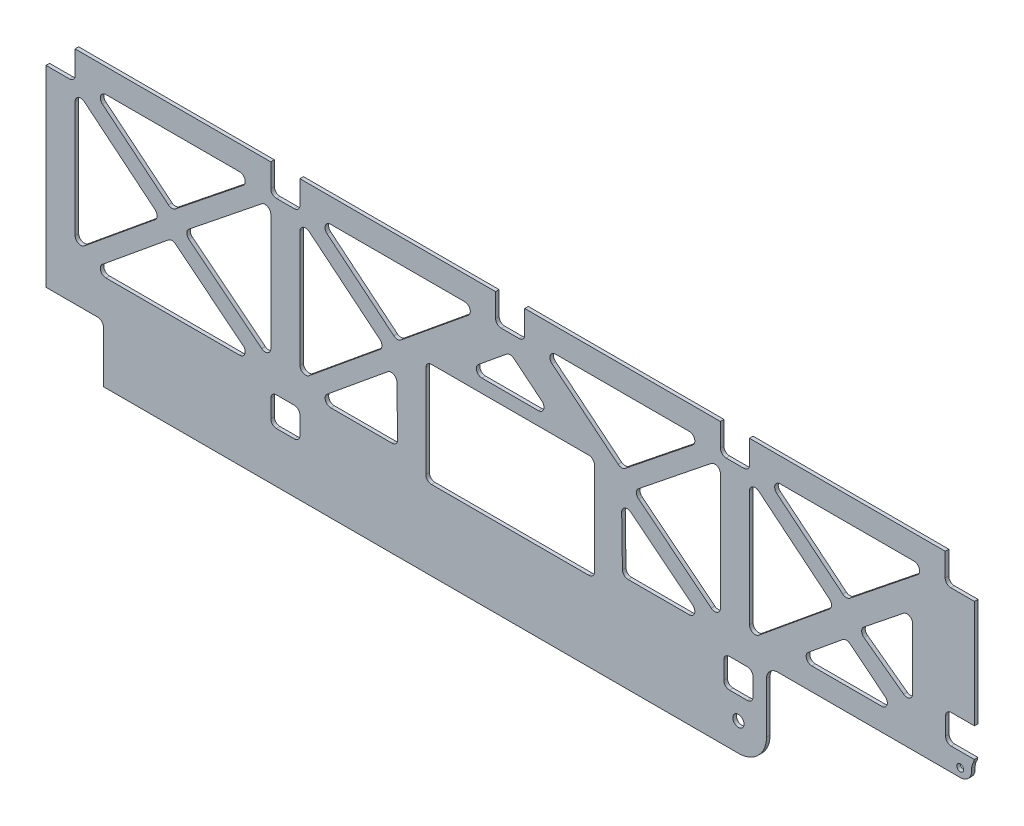
SolidWorks part; units mm, degrees
note: The reader was unsure of these and kept them because the rebuilt part matched: thickness of "Brida base1", "Chapa metálica1", "Chapa metálica23", "Chapa metálica27", "Chapa metálica32", "Chapa metálica33", "Chapa metálica34", "Chapa metálica35", "Chapa metálica36", "Chapa metálica37", "Chapa metálica38", "Chapa metálica39", "Chapa metálica40", "Chapa metálica41", "Chapa metálica42", "Chapa metálica43", "Chapa metálica44", "Chapa metálica45", "Chapa metálica46", "Chapa metálica47", "Chapa metálica48", "Chapa metálica49", "Chapa metálica50", "Chapa metálica51", "Chapa metálica52", "Chapa metálica53", "Chapa metálica54", "Chapa metálica55", "Chapa metálica56", "Chapa metálica57", "Chapa metálica58", "Chapa metálica59", "Chapa metálica60", "Chapa metálica71".
other "Elemento de detalle13"
other "Elemento de detalle19"
other "Carpeta de soldadura"
material "AISI 1010 Barra de acero laminada en caliente"
ref_plane "Alzado" through (0, 0, 0) normal (0, 0, 1) x (1, 0, 0)
ref_plane "Planta" through (0, 0, 0) normal (0, 1, 0) x (1, 0, 0)
ref_plane "Vista lateral" through (0, 0, 0) normal (1, 0, 0) x (0, 0, -1)
sketch "Croquis1" plane through (0, 0, 0) normal (0, 0, 1) x (1, 0, 0)
  line L1 (-634.7218, 129.9029) -> (1017.2782, 129.9029)
  line L2 (-634.7218, 129.9029) -> (-634.7218, -670.0971)
  line L3 (-634.7218, -670.0971) -> (1017.2782, -670.0971)
  line L4 (1017.2782, 129.9029) -> (1017.2782, -670.0971)
  dimension "D1" = 800
  dimension "D2" = 1652
base flange "Brida base1" sketch "Croquis1" thickness 6.35 reverse thickness direction no parameters "D1"=0.7366
ref_plane "Plano1" through (0, 0, 0) normal (0, 1, 0) x (1, 0, 0)
sketch "Croquis14" plane through (0, 0, -6.35) normal (0, 0, 1) x (1, 0, 0)
  line L0 (-634.7218, 129.9029) -> (-634.7218, -670.0971) construction
  line L1 (-634.7218, -670.0971) -> (1017.2782, -670.0971) construction
  line L2 (-634.7218, -174.1971) -> (-582.9218, -174.1971)
  line L3 (965.2782, -174.1971) -> (1028.4048, -174.1971)
  line L4 (-451.2573, -29.958) -> (-582.9218, -29.958) construction
  line L5 (-634.7218, -174.1971) -> (-634.7218, -225.9971)
  line L6 (-634.7218, -225.9971) -> (-582.9218, -225.9971)
  line L7 (-582.9218, -174.1971) -> (-582.9218, -225.9971)
  line L8 (1017.2782, 129.9029) -> (-634.7218, 129.9029) construction
  line L9 (-234.7218, -174.1971) -> (-182.9218, -174.1971)
  line L10 (-234.7218, -174.1971) -> (-234.7218, -225.9971)
  line L11 (1017.2782, 129.9029) -> (-634.7218, 129.9029) construction
  line L12 (-234.7218, -225.9971) -> (-182.9218, -225.9971)
  line L13 (-410.7218, 129.9029) -> (-410.7218, -670.0971) construction
  line L14 (-182.9218, -174.1971) -> (-182.9218, -225.9971)
  line L15 (165.2782, -174.1971) -> (217.0782, -174.1971)
  line L16 (165.2782, -174.1971) -> (165.2782, -225.9971)
  line L17 (165.2782, -225.9971) -> (217.0782, -225.9971)
  line L18 (217.0782, -174.1971) -> (217.0782, -225.9971)
  line L19 (565.2782, -174.1971) -> (617.0782, -174.1971)
  line L20 (565.2782, -174.1971) -> (565.2782, -225.9971)
  line L21 (565.2782, -225.9971) -> (617.0782, -225.9971)
  line L22 (617.0782, -174.1971) -> (617.0782, -225.9971)
  line L23 (165.2782, 130.8029) -> (217.0782, 130.8029)
  line L24 (589.2782, 129.9029) -> (589.2782, -670.0971) construction
  line L25 (89.2782, 129.9029) -> (89.2782, -670.0971) construction
  line L26 (565.2782, 130.8029) -> (617.0782, 130.8029)
  line L27 (565.2782, 130.8029) -> (565.2782, 79.0029)
  line L28 (565.2782, 79.0029) -> (617.0782, 79.0029)
  line L29 (617.0782, 130.8029) -> (617.0782, 79.0029)
  line L30 (-582.9218, 78.1029) -> (-582.9218, -138.0188)
  line L31 (-582.9218, -138.0188) -> (-451.2573, -29.958)
  line L32 (-451.2573, -29.958) -> (-582.9218, 78.1029)
  line L33 (-556.1038, 94.9029) -> (-268.9149, 94.9029)
  line L34 (-268.9149, 94.9029) -> (-410.7218, -24.4164)
  line L35 (-410.7218, -24.4164) -> (-556.1038, 94.9029)
  line L36 (-234.7218, 31.6626) -> (-234.7218, -174.0284)
  line L37 (-234.7218, -174.0284) -> (-327.6777, -27.1786)
  line L38 (965.2782, -174.1971) -> (965.2782, -225.9971)
  line L39 (215.2782, -200.0989) -> (315.2782, -200.0989) construction
  line L40 (617.0782, 78.1029) -> (617.0782, -170.9006)
  line L41 (965.2782, -225.9971) -> (1028.4048, -225.9971)
  line L42 (1028.4048, -174.1971) -> (1028.4048, -225.9971)
  line L43 (-634.7218, 129.9029) -> (-634.7218, -670.0971) construction
  line L44 (768.7748, -46.3989) -> (617.0782, 78.1029)
  line L45 (617.0782, -170.9006) -> (768.7748, -46.3989)
  line L46 (-634.7218, -670.0971) -> (1017.2782, -670.0971) construction
  line L47 (1017.2782, -670.0971) -> (1017.2782, 129.9029) construction
  line L48 (-10.7218, -380.9849) -> (-8.92, -500.3041)
  line L49 (-327.6777, -27.1786) -> (-234.7218, 31.6626)
  line L50 (389.2782, -380.9849) -> (391.08, -500.3041)
  line L51 (191.1782, -255.9971) -> (112.945, -319.9971)
  line L52 (-234.7218, 79.0029) -> (-634.7218, -174.1971) construction
  line L53 (-634.7218, -174.1971) -> (-631.748, -174.0915) construction
  line L54 (112.945, -319.9971) -> (269.4115, -319.9971)
  line L55 (269.4115, -319.9971) -> (191.1782, -255.9971)
  line L56 (191.1782, -225.9971) -> (191.1782, -255.9971) construction
  line L57 (191.1782, -255.9971) -> (191.1782, -319.9971) construction
  line L84 (165.2782, 130.8029) -> (165.2782, 79.0029)
  line L85 (165.2782, 79.0029) -> (217.0782, 79.0029)
  line L86 (217.0782, 130.8029) -> (217.0782, 79.0029)
  line L87 (-234.7218, 130.8029) -> (-182.9218, 130.8029)
  line L88 (-234.7218, 130.8029) -> (-234.7218, 79.0029)
  line L89 (-234.7218, 79.0029) -> (-182.9218, 79.0029)
  line L90 (-182.9218, 130.8029) -> (-182.9218, 79.0029)
  line L91 (-634.7218, 130.8029) -> (-582.9218, 130.8029)
  line L92 (-634.7218, 130.8029) -> (-634.7218, 79.0029)
  line L93 (-634.7218, 79.0029) -> (-582.9218, 79.0029)
  line L94 (-582.9218, 130.8029) -> (-582.9218, 79.0029)
  line L95 (-182.9218, 78.1029) -> (-182.9218, -174.0284)
  line L96 (-182.9218, -174.0284) -> (-31.2252, -46.3989)
  line L97 (-31.2252, -46.3989) -> (-182.9218, 78.1029)
  line L98 (-156.1038, 94.9029) -> (138.2639, 94.9029)
  line L99 (138.2639, 94.9029) -> (-10.7218, -24.4164)
  line L100 (-10.7218, -24.4164) -> (-156.1038, 94.9029)
  line L101 (165.2782, 78.1029) -> (165.2782, -170.9006)
  line L102 (165.2782, -170.9006) -> (9.8215, -46.3989)
  line L103 (9.8215, -46.3989) -> (165.2782, 78.1029)
  line L107 (-31.2252, -46.3989) -> (-182.9218, -46.3989) construction
  line L108 (217.0782, 78.1029) -> (217.0782, -170.9006)
  line L109 (217.0782, -170.9006) -> (368.7748, -46.3989)
  line L110 (368.7748, -46.3989) -> (217.0782, 78.1029)
  line L111 (243.8962, 94.9029) -> (538.2639, 94.9029)
  line L112 (538.2639, 94.9029) -> (389.2782, -24.4164)
  line L113 (389.2782, -24.4164) -> (243.8962, 94.9029)
  line L114 (565.2782, 78.1029) -> (565.2782, -170.9006)
  line L115 (565.2782, -170.9006) -> (409.8215, -46.3989)
  line L116 (409.8215, -46.3989) -> (565.2782, 78.1029)
  line L120 (368.7748, -46.3989) -> (217.0782, -46.3989) construction
  line L124 (643.8962, 94.9029) -> (938.2639, 94.9029)
  line L125 (938.2639, 94.9029) -> (789.2782, -24.4164)
  line L126 (789.2782, -24.4164) -> (643.8962, 94.9029)
  line L127 (965.2782, 78.1029) -> (965.2782, -170.9006)
  line L128 (965.2782, -170.9006) -> (809.8215, -46.3989)
  line L129 (809.8215, -46.3989) -> (965.2782, 78.1029)
  line L134 (-182.9218, -234.5006) -> (-182.9218, -483.5041)
  line L135 (-182.9218, -483.5041) -> (-31.2252, -359.0024)
  line L136 (-31.2252, -359.0024) -> (-182.9218, -234.5006)
  line L137 (-156.1038, -217.7006) -> (138.2639, -217.7006)
  line L138 (138.2639, -217.7006) -> (-9.4746, -338.5606)
  line L139 (-9.4746, -338.5606) -> (-156.1038, -217.7006)
  line L143 (-10.7218, -380.9849) -> (-156.1038, -500.3041)
  line L145 (-156.1038, -500.3041) -> (-8.92, -500.3041)
  line L146 (-31.2252, -359.0024) -> (-182.9218, -359.0024) construction
  line L150 (243.8824, -217.7174) -> (538.2501, -217.7174)
  line L151 (538.2501, -217.7174) -> (389.4543, -336.805)
  line L152 (389.4543, -336.805) -> (243.8824, -217.7174)
  line L153 (565.2782, -234.5006) -> (565.2782, -483.5041)
  line L154 (565.2782, -483.5041) -> (409.8215, -359.0024)
  line L155 (409.8215, -359.0024) -> (565.2782, -234.5006)
  line L157 (538.2639, -500.3041) -> (389.2782, -380.9849)
  line L158 (391.08, -500.3041) -> (538.2639, -500.3041)
  line L160 (617.0782, -234.5006) -> (617.0782, -483.5041)
  line L161 (617.0782, -483.5041) -> (768.7748, -359.0024)
  line L162 (768.7748, -359.0024) -> (617.0782, -234.5006)
  line L163 (643.8962, -217.7006) -> (938.2639, -217.7006)
  line L164 (938.2639, -217.7006) -> (789.2782, -337.0198)
  line L165 (789.2782, -337.0198) -> (643.8962, -217.7006)
  line L166 (907.2782, -294.3999) -> (907.2782, -443.7235)
  line L167 (907.2782, -443.7235) -> (810.208, -372.1413)
  line L168 (810.208, -372.1413) -> (907.2782, -294.3999)
  line L169 (789.2782, -396.7899) -> (699.9586, -470.0971)
  line L170 (880.8119, -470.0971) -> (789.2782, -396.7899)
  line L171 (699.9586, -470.0971) -> (880.8119, -470.0971)
  line L172 (768.7748, -359.0024) -> (617.0782, -359.0024) construction
  line L173 (-582.9218, -234.5006) -> (-582.9218, -483.5041)
  line L174 (-582.9218, -483.5041) -> (-431.2252, -359.0024)
  line L175 (-431.2252, -359.0024) -> (-582.9218, -234.5006)
  line L176 (-556.1038, -217.7006) -> (-261.7361, -217.7006)
  line L177 (-261.7361, -217.7006) -> (-410.7218, -337.0198)
  line L178 (-410.7218, -337.0198) -> (-556.1038, -217.7006)
  line L179 (-234.7218, -234.5006) -> (-234.7218, -483.5041)
  line L180 (-234.7218, -483.5041) -> (-390.1785, -359.0024)
  line L181 (-390.1785, -359.0024) -> (-234.7218, -234.5006)
  line L182 (-410.7218, -380.9849) -> (-556.1038, -500.3041)
  line L183 (-261.7361, -500.3041) -> (-410.7218, -380.9849)
  line L184 (-556.1038, -500.3041) -> (-261.7361, -500.3041)
  line L185 (-431.2252, -359.0024) -> (-582.9218, -359.0024) construction
  dimension "D21" = 30
  dimension "D22" = 64
  dimension "D3" = 0
  dimension "D4" = 2
  dimension "D5" = 51.8
  dimension "D6" = 51.8
  dimension "D7" = 51.8
  dimension "D8" = 304.1
  dimension "D9" = 2
  dimension "D10" = 2
  dimension "D11" = 2
  dimension "D12" = 4
  dimension "D13" = 2
  dimension "D14" = 224
  dimension "D15" = 40
  dimension "D16" = 400
  dimension "D17" = 35
  dimension "D18" = 400
  dimension "D19" = 200
  dimension "D20" = 110
  dimension "D23" = 63
  dimension "D27" = 30
  dimension "D29" = 1000
extrude "Cortar-Extruir1" cut sketch "Croquis14" along normal through all
ref_plane "Plano5" through (0, -200.0971, 0) normal (0, 1, 0) x (1, 0, 0)
ref_plane "Plano6" through (0, -40.0971, 0) normal (0, 1, 0) x (1, 0, 0)
ref_plane "Plano3" through (0, -420.0971, 0) normal (0, -1, 0) x (-1, 0, 0)
fillet "Redondeo1" radius 10 60 edges at (-451.2573, -29.958, -3.175) (-268.9149, 94.9029, -3.175) (-556.1038, 94.9029, -3.175) (880.8119, -470.0971, -3.175) (907.2782, -443.7235, -3.175) (617.0782, -483.5041, -3.175) (699.9586, -470.0971, -3.175) (617.0782, -225.9971, -3.175) (617.0782, -234.5006, -3.175) (643.8962, -217.7006, -3.175) (938.2639, -217.7006, -3.175) (907.2782, -294.3999, -3.175) (768.7748, -359.0024, -3.175) (789.2782, -337.0198, -3.175) (789.2782, -396.7899, -3.175) (810.208, -372.1413, -3.175) (-261.7361, -217.7006, -3.175) (-556.1038, -217.7006, -3.175) (-556.1038, -500.3041, -3.175) (-582.9218, -483.5041, -3.175) (-390.1785, -359.0024, -3.175) (-410.7218, -380.9849, -3.175) (-431.2252, -359.0024, -3.175) (-182.9218, -234.5006, -3.175) (217.0782, -170.9006, -3.175) (243.8962, 94.9029, -3.175) (217.0782, 78.1029, -3.175) (-182.9218, -174.0284, -3.175) (138.2639, -217.7006, -3.175) (-156.1038, -217.7006, -3.175) (-31.2252, -46.3989, -3.175) (-10.7218, -24.4164, -3.175) (165.2782, 78.1029, -3.175) (-156.1038, 94.9029, -3.175) (-261.7361, -500.3041, -3.175) (243.8824, -217.7174, -3.175) (538.2639, -500.3041, -3.175) (409.8215, -359.0024, -3.175) (538.2501, -217.7174, -3.175) (368.7748, -46.3989, -3.175) (409.8215, -46.3989, -3.175) (538.2639, 94.9029, -3.175) (643.8962, 94.9029, -3.175) (789.2782, -24.4164, -3.175) (809.8215, -46.3989, -3.175) (965.2782, -170.9006, -3.175) (938.2639, 94.9029, -3.175) (-182.9218, 78.1029, -3.175) (617.0782, -170.9006, -3.175) (-234.7218, 31.6626, -3.175) (-582.9218, -225.9971, -3.175) (-234.7218, -225.9971, -3.175) (-182.9218, -225.9971, -3.175) (217.0782, -225.9971, -3.175) (165.2782, -225.9971, -3.175) (965.2782, -225.9971, -3.175) (-9.4746, -338.5606, -3.175) (-31.2252, -359.0024, -3.175) (269.4115, -319.9971, -3.175) (191.1782, -255.9971, -3.175)
ref_plane "Plano7" through (0, -476.0971, 0) normal (0, -1, 0) x (-1, 0, 0)
ref_plane "Plano8" through (-410.7218, 0, 0) normal (-1, 0, 0) x (0, 0, 1)
ref_plane "Plano9" through (89.2782, 0, 0) normal (-1, 0, 0) x (0, 0, 1)
ref_plane "Plano10" through (591.1782, 0, 0) normal (-1, 0, 0) x (0, 0, 1)
ref_plane "Plano11" through (0, 104.0029, 0) normal (0, 1, 0) x (1, 0, 0)
sketch "Croquis15" plane through (0, 0, -6.35) normal (0, 0, -1) x (-1, 0, 0)
  line L0 (234.7218, 79.0029) -> (634.7218, -174.1971)
  line L1 (634.7218, -174.1971) -> (723.5953, -174.1971)
  line L2 (723.5953, -174.1971) -> (723.5953, 158.5241)
  line L3 (723.5953, 158.5241) -> (234.7218, 158.5241)
  line L4 (234.7218, 158.5241) -> (234.7218, 79.0029)
extrude "Cortar-Extruir2" cut sketch "Croquis15" against normal blind 10 normal cut yes
sketch "Croquis16" plane through (0, 0, -6.35) normal (0, 0, -1) x (-1, 0, 0)
  line L1 (-1017.2782, -174.1971) -> (834.4945, -174.1971)
  line L2 (-1017.2782, -174.1971) -> (-1017.2782, 472.6355)
  line L3 (-1017.2782, 472.6355) -> (834.4945, 472.6355)
  line L4 (834.4945, -174.1971) -> (834.4945, 472.6355)
extrude "Cortar-Extruir3" cut sketch "Croquis16" against normal blind 10 normal cut yes
sketch "Croquis17" plane through (0, 0, -6.35) normal (0, 0, -1) x (-1, 0, 0)
  line L0 (-965.2782, -215.9971) -> (-611.5841, -506.3181) construction
  line L1 (-1017.2782, -670.0971) -> (-1017.2782, -225.9971) construction
  dimension "D1" = 50.62
hole_wizard "Taladro de margen para M81" [suppressed] positions "Croquis19" profile "Croquis18" hole size "M8" standard "Ansi Metric"
sketch "Croquis19" plane through (0, 0, -6.35) normal (0, 0, -1) x (-1, 0, 0)
  line L0 (-965.2782, -215.9971) -> (-611.5841, -506.3181) construction
  line L1 (-1017.2782, -670.0971) -> (-1017.2782, -225.9971) construction
  line L3 (-591.1782, -225.9971) -> (-591.1782, -587.6273) construction
  line L4 (-575.2782, -225.9971) -> (-607.0782, -225.9971) construction
  line L6 (-175.2782, -225.9971) -> (-207.0782, -225.9971) construction
  line L7 (-191.1782, -225.9971) -> (-191.1782, -615.5767) construction
  line L9 (-965.2782, -215.9971) -> (-611.5841, -506.3181) construction
  line L11 (-217.0782, -215.9971) -> (-570.7724, -506.3181) construction
  line L12 (-165.2782, -215.9971) -> (188.4159, -506.3181) construction
  line L13 (582.9218, -215.9971) -> (229.2276, -506.3181) construction
  point P0 (-944.3982, -233.136)
  point P7 (-878.6971, -287.0651)
  point P9 (-812.9959, -340.9943)
  point P11 (-747.2947, -394.9235)
  point P13 (-681.5935, -448.8526)
  point P15 (-615.8923, -502.7818)
  point P49 (-566.4642, -502.7818)
  point P50 (-500.763, -448.8526)
  point P51 (-435.0618, -394.9235)
  point P52 (-369.3606, -340.9943)
  point P53 (-303.6594, -287.0651)
  point P54 (-237.9582, -233.136)
  point P59 (-144.3982, -233.136)
  point P60 (-78.6971, -287.0651)
  point P61 (-12.9959, -340.9943)
  point P62 (52.7053, -394.9235)
  point P63 (118.4065, -448.8526)
  point P64 (184.1077, -502.7818)
  point P65 (233.5358, -502.7818)
  point P66 (299.237, -448.8526)
  point P67 (364.9382, -394.9235)
  point P68 (430.6394, -340.9943)
  point P69 (496.3406, -287.0651)
  point P70 (562.0418, -233.136)
  dimension "D1" = 72.88
  dimension "D2" = 85
  dimension "D3" = 85
  dimension "D4" = 85
  dimension "D5" = 85
  dimension "D6" = 85
sketch "Croquis18" plane through (944.3982, -233.136, -6.35) normal (1, 0, 0) x (0, 1, 0)
  line L0 (0, 0) -> (0, 6.35)
  line L1 (0, 6.35) -> (4.5, 6.35)
  line L2 (4.5, 6.35) -> (4.5, 0)
  line L5 (4.5, 0) -> (0, 0)
  line L11 (0, -6.35) -> (0, 107.95) construction
  dimension "Diámetro de taladro hasta el siguiente" = 9
  dimension "Profundidad de taladro hasta el siguiente" = 6.35
sketch "Croquis22" plane through (0, 0, 0) normal (0, 0, -1) x (-1, 0, 0)
  line L0 (-1017.2782, -670.0971) -> (-1017.2782, -225.9971) construction
  line L1 (-1017.2782, -670.0971) -> (-647.2782, -670.0971)
  line L2 (-1017.2782, -670.0971) -> (-1017.2782, -510.0971)
  line L3 (-1017.2782, -510.0971) -> (-647.2782, -510.0971)
  line L4 (-647.2782, -670.0971) -> (-647.2782, -510.0971)
  line L5 (-1017.2782, -480.0971) -> (-1012.2782, -480.0971)
  line L6 (-1017.2782, -480.0971) -> (-1017.2782, -510.0971)
  line L7 (-1017.2782, -510.0971) -> (-1012.2782, -510.0971)
  line L8 (-727.9054, -470.0971) -> (-852.3285, -470.0971) construction
  line L9 (-1012.2782, -480.0971) -> (-1012.2782, -510.0971)
  dimension "D1" = 40
  dimension "D2" = 370
  dimension "D3" = 30
  dimension "D4" = 5
extrude "Cortar-Extruir4" cut sketch "Croquis22" along normal blind 10 contours L4 L1 L2 L3 | L5 L9 L3 L6 normal cut yes
fillet "Redondeo2" radius 50 1 edges at (647.2782, -670.0971, -3.175)
fillet "Redondeo4" radius 20 4 edges at (-634.7218, -670.0971, -3.175) (647.2782, -510.0971, -3.175) (1017.2782, -480.0971, -3.175) (1012.2782, -510.0971, -3.175)
sketch "Croquis24" plane through (0, 0, 0) normal (0, 0, 1) x (1, 0, 0)
  line L0 (-614.7218, -670.0971) -> (597.2782, -670.0971) construction
  line L3 (667.2782, -510.0971) -> (992.2782, -510.0971) construction
  line L4 (1012.2782, -480.0971) -> (1012.2782, -490.0971) construction
  line L6 (647.2782, -620.0971) -> (647.2782, -530.0971) construction
  circle A1 centre (597.2782, -620.0971) radius 10
  circle A2 centre (991.8782, -495.0971) radius 6.1
  dimension "D2" = 20
  dimension "D3" = 12.2
  dimension "D6" = 50
  dimension "D1" = 50
  dimension "D4" = 20.4
  dimension "D5" = 15
extrude "Cortar-Extruir5" cut sketch "Croquis24" against normal blind 10 normal cut yes
sketch "Croquis26" plane through (0, 0, 0) normal (0, 0, 1) x (1, 0, 0)
  line L0 (647.2782, -620.0971) -> (647.2782, -530.0971) construction
  line L1 (623.1782, -580.5971) -> (571.3782, -580.5971)
  line L2 (623.1782, -580.5971) -> (623.1782, -528.7971)
  line L3 (623.1782, -528.7971) -> (571.3782, -528.7971)
  line L4 (571.3782, -580.5971) -> (571.3782, -528.7971)
  line L5 (-614.7218, -670.0971) -> (597.2782, -670.0971) construction
  line L6 (1017.7782, -469.6371) -> (965.9782, -469.6371)
  line L7 (1017.7782, -469.6371) -> (1017.7782, -417.8371)
  line L8 (1017.7782, -417.8371) -> (965.9782, -417.8371)
  line L9 (965.9782, -469.6371) -> (965.9782, -417.8371)
  line L10 (-182.9218, -580.5971) -> (-234.7218, -580.5971)
  line L11 (667.2782, -510.0971) -> (992.2782, -510.0971) construction
  line L12 (-182.9218, -580.5971) -> (-182.9218, -528.7971)
  line L13 (991.8782, -417.8371) -> (991.8782, -469.6371) construction
  line L14 (991.8782, -488.9971) -> (991.8782, -501.1971) construction
  line L15 (-182.9218, -528.7971) -> (-234.7218, -528.7971)
  line L16 (-234.7218, -580.5971) -> (-234.7218, -528.7971)
  line L17 (-532.6218, -670.0971) -> (-634.7218, -670.0971)
  line L18 (-532.6218, -670.0971) -> (-532.6218, -567.9971)
  line L19 (-532.6218, -567.9971) -> (-634.7218, -567.9971)
  line L20 (-634.7218, -670.0971) -> (-634.7218, -567.9971)
  line L21 (-208.8218, -528.7971) -> (-208.8218, -225.9971) construction
  line L22 (-224.7218, -225.9971) -> (-192.9218, -225.9971) construction
  line L23 (-634.7218, -225.9971) -> (-634.7218, -650.0971) construction
  circle A0 centre (991.8782, -495.0971) radius 6.1 construction
  dimension "D1" = 24.1
  dimension "D2" = 51.8
  dimension "D3" = 51.8
  dimension "D4" = 89.5
  dimension "D5" = 51.8
  dimension "D6" = 51.8
  dimension "D7" = 40.46
  dimension "D8" = 2
  dimension "D10" = 102.1
  dimension "D9" = 102.1
extrude "Cortar-Extruir6" cut sketch "Croquis26" against normal blind 10 normal cut yes
sketch "Croquis27" plane through (0, 0, 0) normal (0, 0, 1) x (1, 0, 0)
  line L1 (41.1782, -528.7971) -> (341.1782, -528.7971)
  line L2 (41.1782, -528.7971) -> (41.1782, -343.7971)
  line L3 (41.1782, -343.7971) -> (341.1782, -343.7971)
  line L4 (341.1782, -528.7971) -> (341.1782, -343.7971)
  line L5 (41.1782, -528.7971) -> (341.1782, -343.7971) construction
  line L6 (41.1782, -343.7971) -> (341.1782, -528.7971) construction
  line L7 (-182.9218, -528.7971) -> (-234.7218, -528.7971) construction
  line L9 (191.1782, -225.9971) -> (191.1782, -343.7971) construction
  line L11 (175.2782, -225.9971) -> (207.0782, -225.9971) construction
  point P0 (191.1782, -436.2971)
  dimension "D1" = 185
  dimension "D2" = 300
extrude "Cortar-Extruir7" cut sketch "Croquis27" against normal blind 10 contours L3 L4 L1 L2 normal cut yes
fillet "Redondeo5" radius 10 19 edges at (623.1782, -580.5971, -3.175) (571.3782, -580.5971, -3.175) (623.1782, -528.7971, -3.175) (571.3782, -528.7971, -3.175) (965.9782, -469.6371, -3.175) (965.9782, -417.8371, -3.175) (-234.7218, -580.5971, -3.175) (-182.9218, -580.5971, -3.175) (-182.9218, -528.7971, -3.175) (-234.7218, -528.7971, -3.175) (-532.6218, -567.9971, -3.175) (41.1782, -528.7971, -3.175) (341.1782, -528.7971, -3.175) (341.1782, -343.7971, -3.175) (41.1782, -343.7971, -3.175) (391.08, -500.3041, -3.175) (389.2782, -380.9849, -3.175) (-8.92, -500.3041, -3.175) (-10.7218, -380.9849, -3.175)
fillet "Redondeo6" radius 20 1 edges at (1012.2782, -480.0971, -3.175)
sketch "Croquis28" plane through (0, 0, 0) normal (0, 0, 1) x (1, 0, 0)
  line L0 (-582.9218, -174.1971) -> (-234.7218, -174.1971) construction
  line L1 (-617.6412, -95.7669) -> (1013.0871, -95.7669)
  line L2 (-617.6412, -95.7669) -> (-617.6412, -174.6971)
  line L3 (-617.6412, -174.6971) -> (1013.0871, -174.6971)
  line L4 (1013.0871, -95.7669) -> (1013.0871, -174.6971)
  dimension "D1" = 0.5
extrude "Cortar-Extruir8" cut sketch "Croquis28" against normal blind 10
sketch "Líneas de pliegue1" [suppressed] plane through (0, 0, 0) normal (0, 1, 0) x (1, 0, 0)
sketch "Cuadro delimitador1" [suppressed] plane through (0, 0, 0) normal (0, 1, 0) x (1, 0, 0)
sheet metal parameters "Chapa metálica1" thickness 6.35 parameters "D1"=0.7366
flat pattern "Chapa desplegada1" [suppressed]
sketch "Líneas de pliegue2" plane through (0, 0, 0) normal (0, 1, 0) x (1, 0, 0)
sketch3d "Cuadro delimitador2" [suppressed]
  line L0 (-634.7218, -670.0971, 0) -> (1037.2782, -670.0971, 0) construction
  line L1 (-634.7218, 129.9029, 0) -> (1037.2782, 129.9029, 0) construction
  line L2 (-634.7218, -670.0971, 0) -> (-634.7218, 129.9029, 0) construction
  line L3 (1037.2782, -670.0971, 0) -> (1037.2782, 129.9029, 0) construction
sheet metal parameters "Chapa metálica23" thickness 6.35 parameters "D1"=0.7366, "D7"=12.7
flat pattern "Chapa desplegada1"
sketch "Líneas de pliegue2" plane through (0, 0, 0) normal (0, 1, 0) x (1, 0, 0)
sketch3d "Cuadro delimitador2" [suppressed]
  line L0 (-634.7218, -370.0971, 0) -> (1165.2782, -370.0971, 0) construction
  line L1 (-634.7218, 129.9029, 0) -> (1165.2782, 129.9029, 0) construction
  line L2 (-634.7218, -370.0971, 0) -> (-634.7218, 129.9029, 0) construction
  line L3 (1165.2782, -370.0971, 0) -> (1165.2782, 129.9029, 0) construction
sheet metal parameters "Chapa metálica27" thickness 6.35 parameters "D1"=0.7366, "D7"=12.7
flat pattern "Chapa desplegada1"
sketch "Líneas de pliegue2" plane through (0, 0, 0) normal (0, 1, 0) x (1, 0, 0)
sketch3d "Cuadro delimitador2" [suppressed]
  line L0 (-634.7218, -670.0971, 0) -> (1165.2782, -670.0971, 0) construction
  line L1 (-634.7218, 129.9029, 0) -> (1165.2782, 129.9029, 0) construction
  line L2 (-634.7218, -670.0971, 0) -> (-634.7218, 129.9029, 0) construction
  line L3 (1165.2782, -670.0971, 0) -> (1165.2782, 129.9029, 0) construction
sheet metal parameters "Chapa metálica29" thickness 12.7 parameters "D1"=0.7366
flat pattern "Chapa desplegada29"
sketch "Líneas de pliegue4" plane through (0, 0, 0) normal (0, 1, 0) x (1, 0, 0)
sketch3d "Cuadro delimitador4" [suppressed]
  line L0 (-119.0982, -238.1302, 0) -> (165.2782, -238.1302, 0) construction
  line L1 (-119.0982, -2.2285, 0) -> (165.2782, -2.2285, 0) construction
  line L2 (-119.0982, -238.1302, 0) -> (-119.0982, -2.2285, 0) construction
  line L3 (165.2782, -238.1302, 0) -> (165.2782, -2.2285, 0) construction
sheet metal parameters "Chapa metálica30" thickness 12.7 parameters "D1"=0.7366
flat pattern "Chapa desplegada30"
sketch "Líneas de pliegue5" plane through (0, 0, 0) normal (0, 1, 0) x (1, 0, 0)
sketch3d "Cuadro delimitador5" [suppressed]
  line L0 (-485.077, -310.0971, 0) -> (205.2782, -310.0971, 0) construction
  line L1 (-485.077, -211.7375, 0) -> (205.2782, -211.7375, 0) construction
  line L2 (-485.077, -310.0971, 0) -> (-485.077, -211.7375, 0) construction
  line L3 (205.2782, -310.0971, 0) -> (205.2782, -211.7375, 0) construction
sheet metal parameters "Chapa metálica31" thickness 12.7 parameters "D1"=0.7366
flat pattern "Chapa desplegada31"
sketch "Líneas de pliegue6" plane through (0, 0, 0) normal (0, 1, 0) x (1, 0, 0)
sketch3d "Cuadro delimitador6" [suppressed]
  line L0 (-484.7218, -29.6275, 0) -> (205.2782, -29.6275, 0) construction
  line L1 (-484.7218, 69.9029, 0) -> (205.2782, 69.9029, 0) construction
  line L2 (-484.7218, -29.6275, 0) -> (-484.7218, 69.9029, 0) construction
  line L3 (205.2782, -29.6275, 0) -> (205.2782, 69.9029, 0) construction
sheet metal parameters "Chapa metálica32" thickness 6.35 parameters "D1"=0.7366
flat pattern "Chapa desplegada1"
sketch "Líneas de pliegue7" plane through (0, 0, 0) normal (0, 1, 0) x (1, 0, 0)
sketch3d "Cuadro delimitador7" [suppressed]
  line L0 (-634.7218, -670.0971, 0) -> (1165.2782, -670.0971, 0) construction
  line L1 (-634.7218, 129.9029, 0) -> (1165.2782, 129.9029, 0) construction
  line L2 (-634.7218, -670.0971, 0) -> (-634.7218, 129.9029, 0) construction
  line L3 (1165.2782, -670.0971, 0) -> (1165.2782, 129.9029, 0) construction
sheet metal parameters "Chapa metálica33" thickness 6.35 parameters "D1"=0.7366
flat pattern "Chapa desplegada33"
sketch "Líneas de pliegue8" plane through (0, 0, 0) normal (0, 1, 0) x (1, 0, 0)
sketch "Cuadro delimitador8" [suppressed] plane through (0, 0, 0) normal (0, 1, 0) x (1, 0, 0)
sheet metal parameters "Chapa metálica34" thickness 6.35 parameters "D1"=0.7366
flat pattern "Chapa desplegada34"
sketch "Líneas de pliegue9" plane through (0, 0, 0) normal (0, 1, 0) x (1, 0, 0)
sketch "Cuadro delimitador9" [suppressed] plane through (0, 0, 0) normal (0, 1, 0) x (1, 0, 0)
sheet metal parameters "Chapa metálica35" thickness 6.35 parameters "D1"=0.7366
flat pattern "Chapa desplegada1"
sketch "Líneas de pliegue10" plane through (0, 0, 0) normal (0, 1, 0) x (1, 0, 0)
sketch3d "Cuadro delimitador10" [suppressed]
  line L0 (-634.7218, -670.0971, 0) -> (1017.2782, -670.0971, 0) construction
  line L1 (-634.7218, 129.9029, 0) -> (1017.2782, 129.9029, 0) construction
  line L2 (-634.7218, -670.0971, 0) -> (-634.7218, 129.9029, 0) construction
  line L3 (1017.2782, -670.0971, 0) -> (1017.2782, 129.9029, 0) construction
sheet metal parameters "Chapa metálica36" thickness 6.35 parameters "D1"=0.7366
flat pattern "Chapa desplegada36"
sketch "Líneas de pliegue11" plane through (0, 0, 0) normal (0, 1, 0) x (1, 0, 0)
sketch "Cuadro delimitador11" [suppressed] plane through (0, 0, 0) normal (0, 1, 0) x (1, 0, 0)
sheet metal parameters "Chapa metálica37" thickness 6.35 parameters "D1"=0.7366
flat pattern "Chapa desplegada1"
sketch "Líneas de pliegue12" plane through (0, 0, 0) normal (0, 1, 0) x (1, 0, 0)
sketch "Cuadro delimitador12" [suppressed] plane through (0, 0, 0) normal (0, 1, 0) x (1, 0, 0)
sheet metal parameters "Chapa metálica38" thickness 6.35 parameters "D1"=0.7366
flat pattern "Chapa desplegada38"
sketch "Líneas de pliegue13" plane through (0, 0, 0) normal (0, 1, 0) x (1, 0, 0)
sketch "Cuadro delimitador13" [suppressed] plane through (0, 0, 0) normal (0, 1, 0) x (1, 0, 0)
sheet metal parameters "Chapa metálica39" thickness 6.35 parameters "D1"=0.7366
flat pattern "Chapa desplegada39"
sketch "Líneas de pliegue14" plane through (0, 0, 0) normal (0, 1, 0) x (1, 0, 0)
sketch "Cuadro delimitador14" [suppressed] plane through (0, 0, 0) normal (0, 1, 0) x (1, 0, 0)
sheet metal parameters "Chapa metálica40" thickness 6.35 parameters "D1"=0.7366
flat pattern "Chapa desplegada40"
sketch "Líneas de pliegue15" plane through (0, 0, 0) normal (0, 1, 0) x (1, 0, 0)
sketch "Cuadro delimitador15" [suppressed] plane through (0, 0, 0) normal (0, 1, 0) x (1, 0, 0)
sheet metal parameters "Chapa metálica41" thickness 6.35 parameters "D1"=0.7366
flat pattern "Chapa desplegada41"
sketch "Líneas de pliegue16" plane through (0, 0, 0) normal (0, 1, 0) x (1, 0, 0)
sketch "Cuadro delimitador16" [suppressed] plane through (0, 0, 0) normal (0, 1, 0) x (1, 0, 0)
sheet metal parameters "Chapa metálica42" thickness 6.35 parameters "D1"=0.7366
flat pattern "Chapa desplegada42"
sketch "Líneas de pliegue17" plane through (0, 0, 0) normal (0, 1, 0) x (1, 0, 0)
sketch "Cuadro delimitador17" [suppressed] plane through (0, 0, 0) normal (0, 1, 0) x (1, 0, 0)
sheet metal parameters "Chapa metálica43" thickness 6.35 parameters "D1"=0.7366
flat pattern "Chapa desplegada43"
sketch "Líneas de pliegue18" plane through (0, 0, 0) normal (0, 1, 0) x (1, 0, 0)
sketch "Cuadro delimitador18" [suppressed] plane through (0, 0, 0) normal (0, 1, 0) x (1, 0, 0)
sheet metal parameters "Chapa metálica44" thickness 6.35 parameters "D1"=0.7366
flat pattern "Chapa desplegada44"
sketch "Líneas de pliegue19" plane through (0, 0, 0) normal (0, 1, 0) x (1, 0, 0)
sketch "Cuadro delimitador19" [suppressed] plane through (0, 0, 0) normal (0, 1, 0) x (1, 0, 0)
sheet metal parameters "Chapa metálica45" thickness 6.35 parameters "D1"=0.7366
flat pattern "Chapa desplegada45"
sketch "Líneas de pliegue20" plane through (0, 0, 0) normal (0, 1, 0) x (1, 0, 0)
sketch "Cuadro delimitador20" [suppressed] plane through (0, 0, 0) normal (0, 1, 0) x (1, 0, 0)
sheet metal parameters "Chapa metálica46" thickness 6.35 parameters "D1"=0.7366
flat pattern "Chapa desplegada46"
sketch "Líneas de pliegue21" plane through (0, 0, 0) normal (0, 1, 0) x (1, 0, 0)
sketch "Cuadro delimitador21" [suppressed] plane through (0, 0, 0) normal (0, 1, 0) x (1, 0, 0)
sheet metal parameters "Chapa metálica47" thickness 6.35 parameters "D1"=0.7366
flat pattern "Chapa desplegada47"
sketch "Líneas de pliegue22" plane through (0, 0, 0) normal (0, 1, 0) x (1, 0, 0)
sketch3d "Cuadro delimitador22" [suppressed]
  line L0 (-11.8337, -225.9971, 0) -> (-8.8218, -225.9971, 0) construction
  line L1 (-11.8337, -223.418, 0) -> (-8.8218, -223.418, 0) construction
  line L2 (-11.8337, -225.9971, 0) -> (-11.8337, -223.418, 0) construction
  line L3 (-8.8218, -225.9971, 0) -> (-8.8218, -223.418, 0) construction
sheet metal parameters "Chapa metálica48" thickness 6.35 parameters "D1"=0.7366
flat pattern "Chapa desplegada48"
sketch "Líneas de pliegue23" plane through (0, 0, 0) normal (0, 1, 0) x (1, 0, 0)
sketch "Cuadro delimitador23" [suppressed] plane through (0, 0, 0) normal (0, 1, 0) x (1, 0, 0)
sheet metal parameters "Chapa metálica49" thickness 6.35 parameters "D1"=0.7366
flat pattern "Chapa desplegada49"
sketch "Líneas de pliegue24" plane through (0, 0, 0) normal (0, 1, 0) x (1, 0, 0)
sketch "Cuadro delimitador24" [suppressed] plane through (0, 0, 0) normal (0, 1, 0) x (1, 0, 0)
sheet metal parameters "Chapa metálica50" thickness 6.35 parameters "D1"=0.7366
flat pattern "Chapa desplegada50"
sketch "Líneas de pliegue25" plane through (0, 0, 0) normal (0, 1, 0) x (1, 0, 0)
sketch "Cuadro delimitador25" [suppressed] plane through (0, 0, 0) normal (0, 1, 0) x (1, 0, 0)
sheet metal parameters "Chapa metálica51" thickness 6.35 parameters "D1"=0.7366
flat pattern "Chapa desplegada51"
sketch "Líneas de pliegue26" plane through (0, 0, 0) normal (0, 1, 0) x (1, 0, 0)
sketch3d "Cuadro delimitador26" [suppressed]
  line L0 (1017.0782, -174.1971, 0) -> (1017.0782, -225.9971, 0) construction
  line L1 (965.2782, -174.1971, 0) -> (965.2782, -225.9971, 0) construction
  line L2 (1017.0782, -174.1971, 0) -> (965.2782, -174.1971, 0) construction
  line L3 (1017.0782, -225.9971, 0) -> (965.2782, -225.9971, 0) construction
sheet metal parameters "Chapa metálica52" thickness 6.35 parameters "D1"=0.7366
flat pattern "Chapa desplegada52"
sketch "Líneas de pliegue27" plane through (0, 0, 0) normal (0, 1, 0) x (1, 0, 0)
sketch3d "Cuadro delimitador27" [suppressed]
  line L0 (565.2782, -225.9971, 0) -> (617.0782, -225.9971, 0) construction
  line L1 (565.2782, -174.1971, 0) -> (617.0782, -174.1971, 0) construction
  line L2 (565.2782, -225.9971, 0) -> (565.2782, -174.1971, 0) construction
  line L3 (617.0782, -225.9971, 0) -> (617.0782, -174.1971, 0) construction
sheet metal parameters "Chapa metálica53" thickness 6.35 parameters "D1"=0.7366
flat pattern "Chapa desplegada53"
sketch "Líneas de pliegue28" plane through (0, 0, 0) normal (0, 1, 0) x (1, 0, 0)
sketch3d "Cuadro delimitador28" [suppressed]
  line L0 (-634.7218, 79.0029, 0) -> (-582.9218, 79.0029, 0) construction
  line L1 (-634.7218, 129.9029, 0) -> (-582.9218, 129.9029, 0) construction
  line L2 (-634.7218, 79.0029, 0) -> (-634.7218, 129.9029, 0) construction
  line L3 (-582.9218, 79.0029, 0) -> (-582.9218, 129.9029, 0) construction
sheet metal parameters "Chapa metálica54" thickness 6.35 parameters "D1"=0.7366
flat pattern "Chapa desplegada1"
sketch "Líneas de pliegue10" plane through (0, 0, 0) normal (0, 1, 0) x (1, 0, 0)
sketch3d "Cuadro delimitador10" [suppressed]
  line L0 (-634.7218, -670.0971, 0) -> (1017.2782, -670.0971, 0) construction
  line L1 (-634.7218, 129.9029, 0) -> (1017.2782, 129.9029, 0) construction
  line L2 (-634.7218, -670.0971, 0) -> (-634.7218, 129.9029, 0) construction
  line L3 (1017.2782, -670.0971, 0) -> (1017.2782, 129.9029, 0) construction
sheet metal parameters "Chapa metálica55" thickness 6.35 parameters "D1"=0.7366
flat pattern "Chapa desplegada1"
sketch "Líneas de pliegue10" plane through (0, 0, 0) normal (0, 1, 0) x (1, 0, 0)
sketch3d "Cuadro delimitador10" [suppressed]
  line L0 (-634.7218, -670.0971, 0) -> (1017.2782, -670.0971, 0) construction
  line L1 (-634.7218, -174.1971, 0) -> (1017.2782, -174.1971, 0) construction
  line L2 (-634.7218, -670.0971, 0) -> (-634.7218, -174.1971, 0) construction
  line L3 (1017.2782, -670.0971, 0) -> (1017.2782, -174.1971, 0) construction
sheet metal parameters "Chapa metálica56" thickness 6.35 parameters "D1"=0.7366
flat pattern "Chapa desplegada1" [suppressed]
sketch "Líneas de pliegue10" plane through (0, 0, 0) normal (0, 1, 0) x (1, 0, 0)
sketch3d "Cuadro delimitador10" [suppressed]
  line L0 (-634.7218, -174.1971, 0) -> (1017.2782, -174.1971, 0) construction
  line L1 (-634.7218, -670.0971, 0) -> (1017.2782, -670.0971, 0) construction
  line L2 (-634.7218, -174.1971, 0) -> (-634.7218, -670.0971, 0) construction
  line L3 (1017.2782, -174.1971, 0) -> (1017.2782, -670.0971, 0) construction
sketch "Croquis17-1" plane through (0, 0, -6.35) normal (0, 0, -1) x (-1, 0, 0)
  line L0 (-965.2782, -215.9971) -> (-611.5841, -506.3181) construction
  line L1 (-1017.2782, -590.0971) -> (-1017.2782, -225.9971) construction
  dimension "D1" = 50.62
sketch "Croquis17-2" plane through (0, 0, -6.35) normal (0, 0, -1) x (-1, 0, 0)
  line L0 (-965.2782, -215.9971) -> (-611.5841, -506.3181) construction
  line L1 (-1017.2782, -490.0971) -> (-1017.2782, -225.9971) construction
  dimension "D1" = 50.62
sketch "Croquis17-3" plane through (0, 0, -6.35) normal (0, 0, -1) x (-1, 0, 0)
  line L0 (-965.2782, -215.9971) -> (-611.5841, -506.3181) construction
  line L1 (-1017.2782, -670.0971) -> (-1017.2782, -225.9971) construction
  dimension "D1" = 50.62
sheet metal parameters "Chapa metálica57" thickness 6.35 parameters "D1"=0.7366
flat pattern "Chapa desplegada1" [suppressed]
sketch "Líneas de pliegue10" plane through (0, 0, 0) normal (0, 1, 0) x (1, 0, 0)
sketch3d "Cuadro delimitador10" [suppressed]
  line L0 (-634.7218, -670.0971, 0) -> (1017.2782, -670.0971, 0) construction
  line L1 (-634.7218, -174.1971, 0) -> (1017.2782, -174.1971, 0) construction
  line L2 (-634.7218, -670.0971, 0) -> (-634.7218, -174.1971, 0) construction
  line L3 (1017.2782, -670.0971, 0) -> (1017.2782, -174.1971, 0) construction
sketch "Croquis17-1" plane through (0, 0, -6.35) normal (0, 0, -1) x (-1, 0, 0)
  line L0 (-965.2782, -215.9971) -> (-611.5841, -506.3181) construction
  line L1 (-1017.2782, -460.3041) -> (-1017.2782, -225.9971) construction
  dimension "D1" = 50.62
sketch "Croquis17-2" plane through (0, 0, -6.35) normal (0, 0, -1) x (-1, 0, 0)
  line L0 (-965.2782, -215.9971) -> (-611.5841, -506.3181) construction
  line L1 (-1017.2782, -490.0971) -> (-1017.2782, -225.9971)
  dimension "D1" = 50.62
sketch "Croquis17-3" plane through (0, 0, -6.35) normal (0, 0, -1) x (-1, 0, 0)
  line L0 (-965.2782, -215.9971) -> (-611.5841, -506.3181) construction
  line L1 (-1017.2782, -670.0971) -> (-1017.2782, -225.9971)
  dimension "D1" = 50.62
sketch "Croquis17-4" plane through (0, 0, -6.35) normal (0, 0, -1) x (-1, 0, 0)
  line L0 (-965.2782, -215.9971) -> (-611.5841, -506.3181) construction
  line L1 (-1017.2782, -670.0971) -> (-1017.2782, -225.9971) construction
  dimension "D1" = 50.62
sheet metal parameters "Chapa metálica58" thickness 6.35 parameters "D1"=0.7366
flat pattern "Chapa desplegada1" [suppressed]
sketch "Líneas de pliegue10" plane through (0, 0, 0) normal (0, 1, 0) x (1, 0, 0)
sketch3d "Cuadro delimitador10" [suppressed]
  line L0 (-634.7218, -174.1971, 0) -> (1017.2782, -174.1971, 0) construction
  line L1 (-634.7218, -670.0971, 0) -> (1017.2782, -670.0971, 0) construction
  line L2 (-634.7218, -174.1971, 0) -> (-634.7218, -670.0971, 0) construction
  line L3 (1017.2782, -174.1971, 0) -> (1017.2782, -670.0971, 0) construction
sketch "Croquis17-1" plane through (0, 0, -6.35) normal (0, 0, -1) x (-1, 0, 0)
  line L0 (-965.2782, -215.9971) -> (-611.5841, -506.3181) construction
  line L1 (-1017.2782, -490.0971) -> (-1017.2782, -225.9971) construction
  dimension "D1" = 50.62
sketch "Croquis17-2" plane through (0, 0, -6.35) normal (0, 0, -1) x (-1, 0, 0)
  line L0 (-965.2782, -215.9971) -> (-611.5841, -506.3181) construction
  line L1 (-1017.2782, -490.0971) -> (-1017.2782, -225.9971)
  dimension "D1" = 50.62
sketch "Croquis17-3" plane through (0, 0, -6.35) normal (0, 0, -1) x (-1, 0, 0)
  line L0 (-965.2782, -215.9971) -> (-611.5841, -506.3181) construction
  line L1 (-1017.2782, -670.0971) -> (-1017.2782, -225.9971)
  dimension "D1" = 50.62
sketch "Croquis17-4" plane through (0, 0, -6.35) normal (0, 0, -1) x (-1, 0, 0)
  line L0 (-965.2782, -215.9971) -> (-611.5841, -506.3181) construction
  line L1 (-1017.2782, -670.0971) -> (-1017.2782, -225.9971)
  dimension "D1" = 50.62
sketch "Croquis17-5" plane through (0, 0, -6.35) normal (0, 0, -1) x (-1, 0, 0)
  line L0 (-965.2782, -215.9971) -> (-611.5841, -506.3181) construction
  line L1 (-1017.2782, -460.3041) -> (-1017.2782, -225.9971) construction
  dimension "D1" = 50.62
sketch "Croquis17-6" plane through (0, 0, -6.35) normal (0, 0, -1) x (-1, 0, 0)
  line L0 (-965.2782, -215.9971) -> (-611.5841, -506.3181) construction
  line L1 (-1017.2782, -490.0971) -> (-1017.2782, -225.9971) construction
  dimension "D1" = 50.62
sheet metal parameters "Chapa metálica59" thickness 6.35 parameters "D1"=0.7366
flat pattern "Chapa desplegada1" [suppressed]
sketch "Líneas de pliegue10" plane through (0, 0, 0) normal (0, 1, 0) x (1, 0, 0)
sketch3d "Cuadro delimitador10" [suppressed]
  line L0 (-634.7218, -174.1971, 0) -> (1017.2782, -174.1972, 0) construction
  line L1 (-634.7218, -670.0971, 0) -> (1017.2782, -670.0972, 0) construction
  line L2 (-634.7218, -174.1971, 0) -> (-634.7218, -670.0971, 0) construction
  line L3 (1017.2782, -174.1972, 0) -> (1017.2782, -670.0972, 0) construction
sketch "Croquis17-1" plane through (0, 0, -6.35) normal (0, 0, -1) x (-1, 0, 0)
  line L0 (-965.2782, -215.9971) -> (-611.5841, -506.3181) construction
  line L1 (-1017.2782, -417.8371) -> (-1017.2782, -225.9971) construction
  dimension "D1" = 50.62
sketch "Croquis17-2" plane through (0, 0, -6.35) normal (0, 0, -1) x (-1, 0, 0)
  line L0 (-965.2782, -215.9971) -> (-611.5841, -506.3181) construction
  line L1 (-1017.2782, -490.0971) -> (-1017.2782, -225.9971)
  dimension "D1" = 50.62
sketch "Croquis17-3" plane through (0, 0, -6.35) normal (0, 0, -1) x (-1, 0, 0)
  line L0 (-965.2782, -215.9971) -> (-611.5841, -506.3181) construction
  line L1 (-1017.2782, -670.0971) -> (-1017.2782, -225.9971)
  dimension "D1" = 50.62
sketch "Croquis17-4" plane through (0, 0, -6.35) normal (0, 0, -1) x (-1, 0, 0)
  line L0 (-965.2782, -215.9971) -> (-611.5841, -506.3181) construction
  line L1 (-1017.2782, -670.0971) -> (-1017.2782, -225.9971)
  dimension "D1" = 50.62
sketch "Croquis17-5" plane through (0, 0, -6.35) normal (0, 0, -1) x (-1, 0, 0)
  line L0 (-965.2782, -215.9971) -> (-611.5841, -506.3181) construction
  line L1 (-1017.2782, -460.3041) -> (-1017.2782, -225.9971)
  dimension "D1" = 50.62
sketch "Croquis17-6" plane through (0, 0, -6.35) normal (0, 0, -1) x (-1, 0, 0)
  line L0 (-965.2782, -215.9971) -> (-611.5841, -506.3181) construction
  line L1 (-1017.2782, -490.0971) -> (-1017.2782, -225.9971)
  dimension "D1" = 50.62
sketch "Croquis17-7" plane through (0, 0, -6.35) normal (0, 0, -1) x (-1, 0, 0)
  line L0 (-965.2782, -215.9971) -> (-611.5841, -506.3181) construction
  line L1 (-1017.2782, -490.0971) -> (-1017.2782, -225.9971) construction
  dimension "D1" = 50.62
sketch "Croquis17-8" plane through (0, 0, -6.35) normal (0, 0, -1) x (-1, 0, 0)
  line L0 (-965.2782, -215.9971) -> (-611.5841, -506.3181) construction
  line L1 (-1017.2782, -490.0971) -> (-1017.2782, -225.9971) construction
  dimension "D1" = 50.62
sketch "Croquis17-9" plane through (0, 0, -6.35) normal (0, 0, -1) x (-1, 0, 0)
  line L0 (-965.2782, -215.9971) -> (-611.5841, -506.3181) construction
  line L1 (-1017.2782, -417.8371) -> (-1017.2782, -225.9971) construction
  dimension "D1" = 50.62
sketch "Croquis17-10" plane through (0, 0, -6.35) normal (0, 0, -1) x (-1, 0, 0)
  line L0 (-965.2782, -215.9971) -> (-611.5841, -506.3181) construction
  line L1 (-1017.2782, -417.8371) -> (-1017.2782, -225.9971) construction
  dimension "D1" = 50.62
sketch "Croquis17-11" plane through (0, 0, -6.35) normal (0, 0, -1) x (-1, 0, 0)
  line L0 (-965.2782, -215.9971) -> (-611.5841, -506.3181) construction
  line L1 (-1017.2782, -417.8371) -> (-1017.2782, -225.9971) construction
  dimension "D1" = 50.62
sheet metal parameters "Chapa metálica60" thickness 6.35 parameters "D1"=0.7366
flat pattern "Chapa desplegada1" [suppressed]
sketch "Líneas de pliegue10" plane through (0, 0, 0) normal (0, 1, 0) x (1, 0, 0)
sketch3d "Cuadro delimitador10" [suppressed]
  line L0 (-634.7218, -174.1971, 0) -> (1017.2782, -174.1972, 0) construction
  line L1 (-634.7218, -670.0971, 0) -> (1017.2782, -670.0972, 0) construction
  line L2 (-634.7218, -174.1971, 0) -> (-634.7218, -670.0971, 0) construction
  line L3 (1017.2782, -174.1972, 0) -> (1017.2782, -670.0972, 0) construction
sketch "Croquis17-1" plane through (0, 0, -6.35) normal (0, 0, -1) x (-1, 0, 0)
  line L0 (-965.2782, -215.9971) -> (-611.5841, -506.3181) construction
  line L1 (-1017.2782, -417.8371) -> (-1017.2782, -225.9971) construction
  dimension "D1" = 50.62
sketch "Croquis17-2" plane through (0, 0, -6.35) normal (0, 0, -1) x (-1, 0, 0)
  line L0 (-965.2782, -215.9971) -> (-611.5841, -506.3181) construction
  line L1 (-1017.2782, -490.0971) -> (-1017.2782, -225.9971)
  dimension "D1" = 50.62
sketch "Croquis17-3" plane through (0, 0, -6.35) normal (0, 0, -1) x (-1, 0, 0)
  line L0 (-965.2782, -215.9971) -> (-611.5841, -506.3181) construction
  line L1 (-1017.2782, -670.0971) -> (-1017.2782, -225.9971)
  dimension "D1" = 50.62
sketch "Croquis17-4" plane through (0, 0, -6.35) normal (0, 0, -1) x (-1, 0, 0)
  line L0 (-965.2782, -215.9971) -> (-611.5841, -506.3181) construction
  line L1 (-1017.2782, -670.0971) -> (-1017.2782, -225.9971)
  dimension "D1" = 50.62
sketch "Croquis17-5" plane through (0, 0, -6.35) normal (0, 0, -1) x (-1, 0, 0)
  line L0 (-965.2782, -215.9971) -> (-611.5841, -506.3181) construction
  line L1 (-1017.2782, -460.3041) -> (-1017.2782, -225.9971)
  dimension "D1" = 50.62
sketch "Croquis17-6" plane through (0, 0, -6.35) normal (0, 0, -1) x (-1, 0, 0)
  line L0 (-965.2782, -215.9971) -> (-611.5841, -506.3181) construction
  line L1 (-1017.2782, -490.0971) -> (-1017.2782, -225.9971)
  dimension "D1" = 50.62
sketch "Croquis17-7" plane through (0, 0, -6.35) normal (0, 0, -1) x (-1, 0, 0)
  line L0 (-965.2782, -215.9971) -> (-611.5841, -506.3181) construction
  line L1 (-1017.2782, -490.0971) -> (-1017.2782, -225.9971)
  dimension "D1" = 50.62
sketch "Croquis17-8" plane through (0, 0, -6.35) normal (0, 0, -1) x (-1, 0, 0)
  line L0 (-965.2782, -215.9971) -> (-611.5841, -506.3181) construction
  line L1 (-1017.2782, -490.0971) -> (-1017.2782, -225.9971)
  dimension "D1" = 50.62
sketch "Croquis17-9" plane through (0, 0, -6.35) normal (0, 0, -1) x (-1, 0, 0)
  line L0 (-965.2782, -215.9971) -> (-611.5841, -506.3181) construction
  line L1 (-1017.2782, -417.8371) -> (-1017.2782, -225.9971)
  dimension "D1" = 50.62
sketch "Croquis17-10" plane through (0, 0, -6.35) normal (0, 0, -1) x (-1, 0, 0)
  line L0 (-965.2782, -215.9971) -> (-611.5841, -506.3181) construction
  line L1 (-1017.2782, -417.8371) -> (-1017.2782, -225.9971)
  dimension "D1" = 50.62
sketch "Croquis17-11" plane through (0, 0, -6.35) normal (0, 0, -1) x (-1, 0, 0)
  line L0 (-965.2782, -215.9971) -> (-611.5841, -506.3181) construction
  line L1 (-1017.2782, -417.8371) -> (-1017.2782, -225.9971)
  dimension "D1" = 50.62
sketch "Croquis17-12" plane through (0, 0, -6.35) normal (0, 0, -1) x (-1, 0, 0)
  line L0 (-965.2782, -215.9971) -> (-611.5841, -506.3181) construction
  line L1 (-1017.2782, -417.8371) -> (-1017.2782, -225.9971) construction
  dimension "D1" = 50.62
sketch "Croquis17-13" plane through (0, 0, -6.35) normal (0, 0, -1) x (-1, 0, 0)
  line L0 (-965.2782, -215.9971) -> (-611.5841, -506.3181) construction
  line L1 (-1017.2782, -417.8371) -> (-1017.2782, -225.9971) construction
  dimension "D1" = 50.62
sketch "Croquis17-14" plane through (0, 0, -6.35) normal (0, 0, -1) x (-1, 0, 0)
  line L0 (-965.2782, -215.9971) -> (-611.5841, -506.3181) construction
  line L1 (-1017.2782, -417.8371) -> (-1017.2782, -225.9971) construction
  dimension "D1" = 50.62
sheet metal parameters "Chapa metálica71" thickness 6.35 parameters "D1"=0.7366
flat pattern "Chapa desplegada1"
sketch "Líneas de pliegue10" plane through (0, 0, 0) normal (0, 1, 0) x (1, 0, 0)
sketch3d "Cuadro delimitador10" [suppressed]
  line L0 (-634.7218, -174.6971, 0) -> (1017.2782, -174.6972, 0) construction
  line L1 (-634.7218, -670.0971, 0) -> (1017.2782, -670.0972, 0) construction
  line L2 (-634.7218, -174.6971, 0) -> (-634.7218, -670.0971, 0) construction
  line L3 (1017.2782, -174.6972, 0) -> (1017.2782, -670.0972, 0) construction
sketch "Croquis17-1" plane through (0, 0, -6.35) normal (0, 0, -1) x (-1, 0, 0)
  line L0 (-965.2782, -215.9971) -> (-611.5841, -506.3181) construction
  line L1 (-1017.2782, -417.8371) -> (-1017.2782, -225.9971) construction
  dimension "D1" = 50.62
sketch "Croquis17-2" plane through (0, 0, -6.35) normal (0, 0, -1) x (-1, 0, 0)
  line L0 (-965.2782, -215.9971) -> (-611.5841, -506.3181) construction
  line L1 (-1017.2782, -490.0971) -> (-1017.2782, -225.9971)
  dimension "D1" = 50.62
sketch "Croquis17-3" plane through (0, 0, -6.35) normal (0, 0, -1) x (-1, 0, 0)
  line L0 (-965.2782, -215.9971) -> (-611.5841, -506.3181) construction
  line L1 (-1017.2782, -670.0971) -> (-1017.2782, -225.9971)
  dimension "D1" = 50.62
sketch "Croquis17-4" plane through (0, 0, -6.35) normal (0, 0, -1) x (-1, 0, 0)
  line L0 (-965.2782, -215.9971) -> (-611.5841, -506.3181) construction
  line L1 (-1017.2782, -670.0971) -> (-1017.2782, -225.9971)
  dimension "D1" = 50.62
sketch "Croquis17-5" plane through (0, 0, -6.35) normal (0, 0, -1) x (-1, 0, 0)
  line L0 (-965.2782, -215.9971) -> (-611.5841, -506.3181) construction
  line L1 (-1017.2782, -460.3041) -> (-1017.2782, -225.9971)
  dimension "D1" = 50.62
sketch "Croquis17-6" plane through (0, 0, -6.35) normal (0, 0, -1) x (-1, 0, 0)
  line L0 (-965.2782, -215.9971) -> (-611.5841, -506.3181) construction
  line L1 (-1017.2782, -490.0971) -> (-1017.2782, -225.9971)
  dimension "D1" = 50.62
sketch "Croquis17-7" plane through (0, 0, -6.35) normal (0, 0, -1) x (-1, 0, 0)
  line L0 (-965.2782, -215.9971) -> (-611.5841, -506.3181) construction
  line L1 (-1017.2782, -490.0971) -> (-1017.2782, -225.9971)
  dimension "D1" = 50.62
sketch "Croquis17-8" plane through (0, 0, -6.35) normal (0, 0, -1) x (-1, 0, 0)
  line L0 (-965.2782, -215.9971) -> (-611.5841, -506.3181) construction
  line L1 (-1017.2782, -490.0971) -> (-1017.2782, -225.9971)
  dimension "D1" = 50.62
sketch "Croquis17-9" plane through (0, 0, -6.35) normal (0, 0, -1) x (-1, 0, 0)
  line L0 (-965.2782, -215.9971) -> (-611.5841, -506.3181) construction
  line L1 (-1017.2782, -417.8371) -> (-1017.2782, -225.9971)
  dimension "D1" = 50.62
sketch "Croquis17-10" plane through (0, 0, -6.35) normal (0, 0, -1) x (-1, 0, 0)
  line L0 (-965.2782, -215.9971) -> (-611.5841, -506.3181) construction
  line L1 (-1017.2782, -417.8371) -> (-1017.2782, -225.9971)
  dimension "D1" = 50.62
sketch "Croquis17-11" plane through (0, 0, -6.35) normal (0, 0, -1) x (-1, 0, 0)
  line L0 (-965.2782, -215.9971) -> (-611.5841, -506.3181) construction
  line L1 (-1017.2782, -417.8371) -> (-1017.2782, -225.9971)
  dimension "D1" = 50.62
sketch "Croquis17-12" plane through (0, 0, -6.35) normal (0, 0, -1) x (-1, 0, 0)
  line L0 (-965.2782, -215.9971) -> (-611.5841, -506.3181) construction
  line L1 (-1017.2782, -417.8371) -> (-1017.2782, -225.9971)
  dimension "D1" = 50.62
sketch "Croquis17-13" plane through (0, 0, -6.35) normal (0, 0, -1) x (-1, 0, 0)
  line L0 (-965.2782, -215.9971) -> (-611.5841, -506.3181) construction
  line L1 (-1017.2782, -417.8371) -> (-1017.2782, -225.9971)
  dimension "D1" = 50.62
sketch "Croquis17-14" plane through (0, 0, -6.35) normal (0, 0, -1) x (-1, 0, 0)
  line L0 (-965.2782, -215.9971) -> (-611.5841, -506.3181) construction
  line L1 (-1017.2782, -417.8371) -> (-1017.2782, -225.9971)
  dimension "D1" = 50.62
sketch "Croquis17-15" plane through (0, 0, -6.35) normal (0, 0, -1) x (-1, 0, 0)
  line L0 (-965.2782, -215.9971) -> (-611.5841, -506.3181) construction
  line L1 (-1017.2782, -417.8371) -> (-1017.2782, -225.9971) construction
  dimension "D1" = 50.62
sketch "Croquis17-16" plane through (0, 0, -6.35) normal (0, 0, -1) x (-1, 0, 0)
  line L0 (-965.2782, -215.9971) -> (-611.5841, -506.3181) construction
  line L1 (-1017.2782, -417.8371) -> (-1017.2782, -225.9971) construction
  dimension "D1" = 50.62
